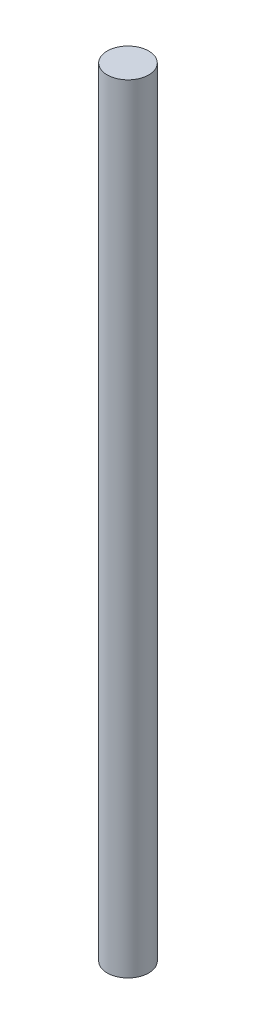
SolidWorks part; units mm, degrees
ref_plane "Front Plane" through (0, 0, 0) normal (0, 0, 1) x (1, 0, 0)
ref_plane "Top Plane" through (0, 0, 0) normal (0, 1, 0) x (1, 0, 0)
ref_plane "Right Plane" through (0, 0, 0) normal (1, 0, 0) x (0, 0, -1)
sketch "Sketch1" plane through (0, 0, 0) normal (0, 1, 0) x (1, 0, 0)
  circle A0 centre (0, 0) radius 4
extrude "Boss-Extrude1" add sketch "Sketch1" along normal blind 150
